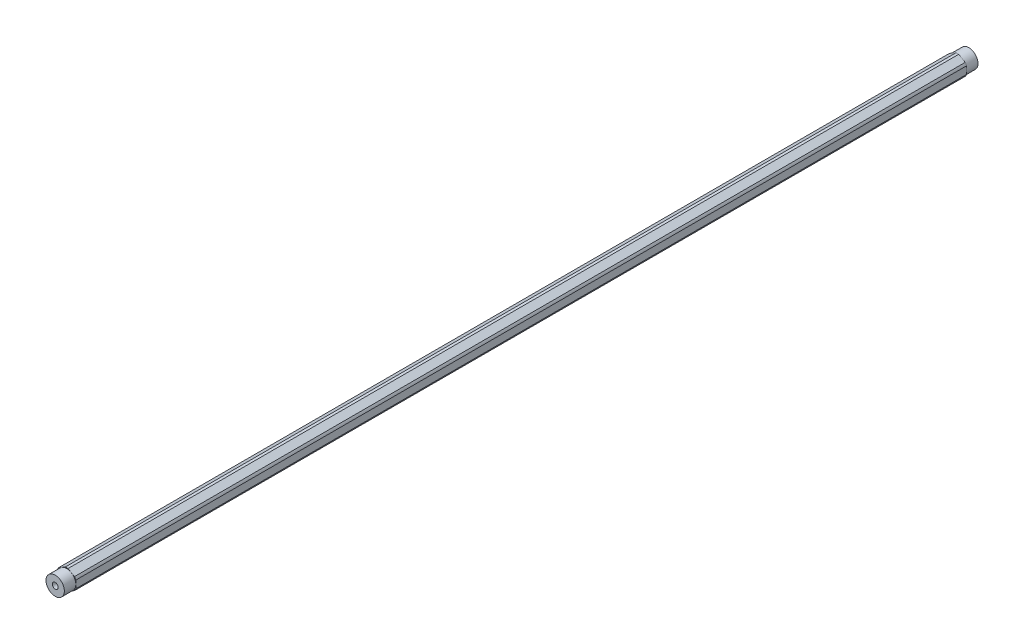
SolidWorks part; units mm, degrees
material "7075-T6 (SN)"
ref_plane "Front Plane" through (0, 0, 0) normal (0, 0, 1) x (1, 0, 0)
ref_plane "Top Plane" through (0, 0, 0) normal (0, 1, 0) x (1, 0, 0)
ref_plane "Right Plane" through (0, 0, 0) normal (1, 0, 0) x (0, 0, -1)
sketch "Sketch2" plane through (0, 0, 0) normal (0, 0, 1) x (1, 0, 0)
  line L1 (0, 7.3323) -> (-6.35, 3.6662)
  line L2 (-6.35, 3.6662) -> (-6.35, -3.6662)
  line L3 (-6.35, -3.6662) -> (0, -7.3323)
  line L4 (0, -7.3323) -> (6.35, -3.6662)
  line L5 (6.35, -3.6662) -> (6.35, 3.6662)
  line L6 (6.35, 3.6662) -> (0, 7.3323)
  circle A0 centre (0, 0) radius 6.35 construction
  circle A2 centre (0, 0) radius 2.0193
  circle A3 centre (0, 0) radius 6.858
  dimension "D1" = 12.7
  dimension "D2" = 13.716
  dimension "D3" = 4.0386
extrude "Boss-Extrude1" add sketch "Sketch2" along normal mid plane 615.95 contours L5 A3 L6 L1 L2 L3 L4 A2 region at (0, 6.6711, 0)
sketch "Sketch7" plane through (0, 0, 307.975) normal (0, 0, 1) x (1, 0, 0)
  circle A0 centre (0, 0) radius 6.35
  dimension "D1" = 12.7
extrude "Boss-Extrude2" add sketch "Sketch7" along normal blind 7.9375
mirror "Mirror1" about plane through (0, 0, 0) normal (0, 0, 1) of "Boss-Extrude2"
hole_wizard "#10-32 Tapped Hole2" positions "3DSketch1" profile "Sketch6" tap size "#10-32" standard "ANSI Inch"
sketch3d "3DSketch1"
  line L0 (0, 0, 315.9125) -> (0, 0, 307.975) construction
  line L1 (0, 0, -315.9125) -> (0, 0, -307.975) construction
  point P14 (0, 0, 315.9125)
  point P18 (0, 0, -315.9125)
sketch "Sketch6" plane through (0, 0, 315.9125) normal (1, 0, 0) x (0, -1, 0)
  line L0 (0, 0) -> (0, 17.5608)
  line L1 (0, 17.5608) -> (2.0193, 16.3474)
  line L2 (2.0193, 16.3474) -> (2.0193, 0)
  line L5 (2.0193, 0) -> (0, 0)
  line L10 (0, 17.5608) -> (-2.0193, 16.3474) construction
  line L11 (0, -6.35) -> (0, 107.95) construction
  dimension "Tap Drill Dia." = 4.0386
  dimension "Tap Drill Depth" = 16.3474
  dimension "Drill Angle" = 118
cosmetic thread "Hole Thread1" parameters "D1"=13.97, "D2"=4.826
cosmetic thread "Hole Thread2" parameters "D1"=13.97, "D2"=4.826
